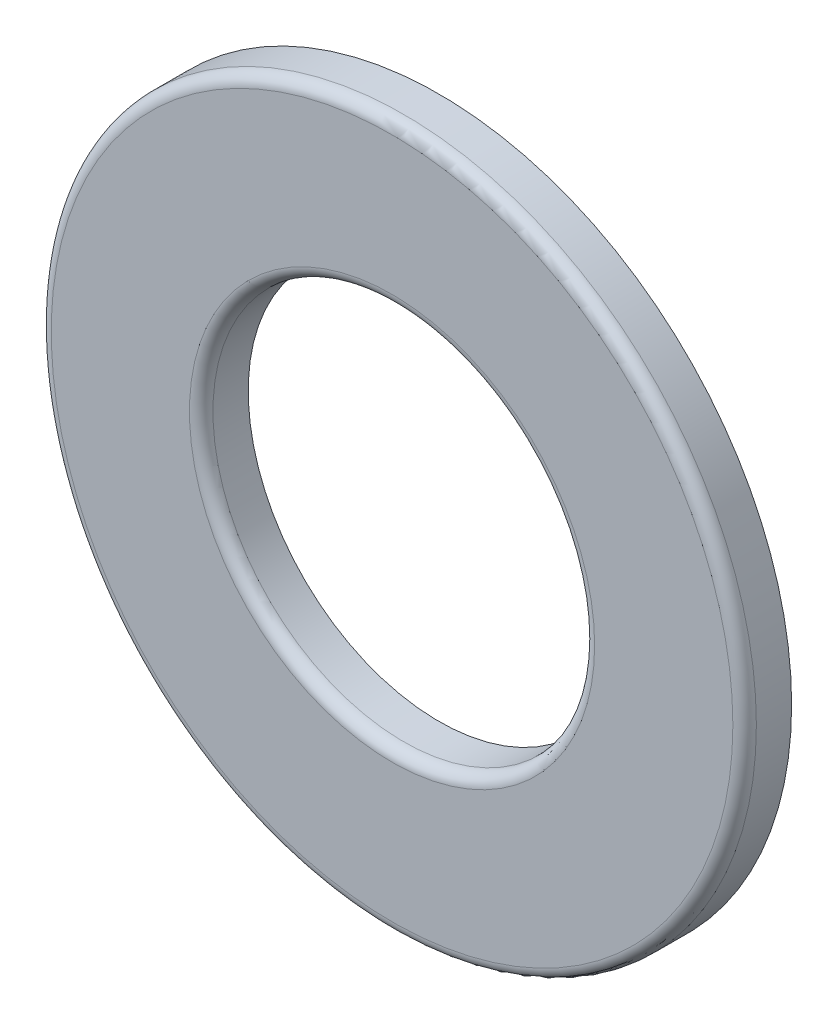
SolidWorks part; units mm, degrees
note: '?' marks a value the reader was unsure of.
other "Imported1" parameters "D1"=0.3175, "TH"=1.0287, "Thickness"=1.27
ref_plane "Front Plane" through (0, 0, 0) normal (0, 0, 1) x (1, 0, 0)
ref_plane "Top Plane" through (0, 0, 0) normal (0, 1, 0) x (1, 0, 0)
ref_plane "Right Plane" through (0, 0, 0) normal (1, 0, 0) x (0, 0, -1)
sketch "Sketch1" plane through (0, 0, 0) normal (0, 0, 1) x (1, 0, 0)
  line L0 (-9.525, 0) -> (9.525, 0) construction
  line L1 (-5.1562, 0) -> (5.1562, 0) construction
  circle A0 centre (0, 0) radius 5.1562 construction
  circle A1 centre (0, 0) radius 9.525 construction
  point P8 (0, 0)
  point P9 (0, 9.525)
  point P11 (5.1562, 0)
  dimension "ID" = 10.3124
  dimension "OD" = 19.05
sketch "Sketch2" plane through (0, 0, 0) normal (1, 0, 0) x (0, 0, -1)
  line L0 (-0.635, 9.525) -> (0.635, 9.525) construction
  point P2 (0, 9.525)
sketch "Sketch3" plane through (0, 0, 0) normal (0, 0, 1) x (1, 0, 0)
  circle A0 centre (0, 0) radius 5.1562
  circle A1 centre (0, 0) radius 9.525
extrude "Boss-Extrude1" add sketch "Sketch3" along normal up to vertex (0.635 mm away) and the other way up to vertex (0.635 mm away) up to point (0, 9.525, 0.635) other way up to point (0, 9.525, -0.635)
fillet "Fillet1" radius 0.3175 2 edges at (9.525, 0, 0.635) (5.1562, 0, 0.635)
ref_axis "Center Axis 1" through (0, 0, 0.3175) along (0, 0, -1)?
equation "\"D1@Fillet1\"=\"Thickness@Sketch2\"/4"
